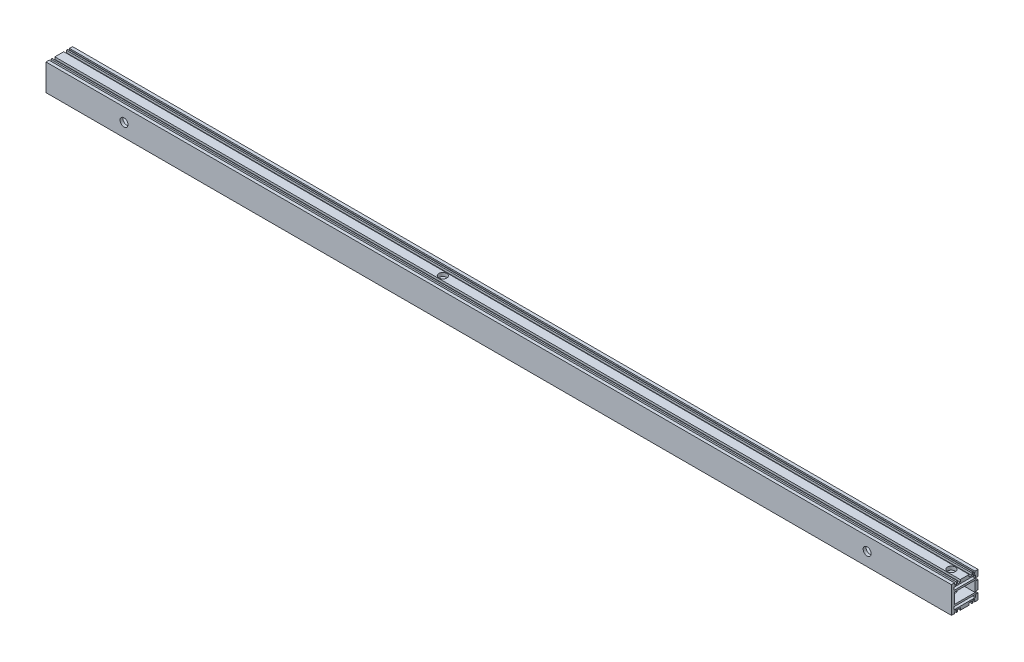
SolidWorks part; units mm, degrees
ref_plane "前视基准面" through (0, 0, 0) normal (0, 0, 1) x (1, 0, 0)
ref_plane "上视基准面" through (0, 0, 0) normal (0, 1, 0) x (1, 0, 0)
ref_plane "右视基准面" through (0, 0, 0) normal (1, 0, 0) x (0, 0, -1)
sketch "草图1" plane through (0, 0, 0) normal (1, 0, 0) x (0, 0, -1)
  line L0 (-15, 15) -> (15, -15) construction
  line L1 (-15, 15) -> (-11.5, 15)
  line L2 (-15, 15) -> (-15, -15)
  line L3 (-15, -15) -> (-11.5, -15)
  line L4 (15, 15) -> (15, 8)
  line L5 (15, 15) -> (-15, -15) construction
  line L6 (-11.5, 15) -> (-11.5, 13.5)
  line L7 (-11.5, 13.5) -> (-11, 13.5)
  line L8 (-11, 13.5) -> (-11, 12)
  line L9 (-11, 12) -> (-9.5, 12)
  line L10 (-9.5, 12) -> (-9.5, 15)
  line L11 (-9.5, 15) -> (-8, 15)
  line L12 (-8, 15) -> (-8, 12.5)
  line L13 (-8, 12.5) -> (-5, 12.5)
  line L14 (-5, 12.5) -> (-5, 15)
  line L15 (-5, 15) -> (5, 15)
  line L16 (0, 21.5201) -> (0, -18.309) construction
  line L17 (0, 55) -> (0, -55) construction
  line L18 (5, 12.5) -> (5, 15)
  line L19 (8, 12.5) -> (5, 12.5)
  line L20 (8, 15) -> (8, 12.5)
  line L21 (9.5, 15) -> (8, 15)
  line L22 (9.5, 12) -> (9.5, 15)
  line L23 (11, 12) -> (9.5, 12)
  line L24 (11, 13.5) -> (11, 12)
  line L25 (11.5, 13.5) -> (11, 13.5)
  line L26 (11.5, 15) -> (11.5, 13.5)
  line L27 (8, 15) -> (9.5, 15)
  line L28 (11.5, 15) -> (15, 15)
  line L29 (-19.8303, 0) -> (22.13, 0) construction
  line L30 (55, 0) -> (-55, 0) construction
  line L31 (8, -15) -> (9.5, -15)
  line L32 (11.5, -15) -> (11.5, -13.5)
  line L33 (11.5, -13.5) -> (11, -13.5)
  line L34 (11, -13.5) -> (11, -12)
  line L35 (11, -12) -> (9.5, -12)
  line L36 (9.5, -12) -> (9.5, -15)
  line L37 (9.5, -15) -> (8, -15)
  line L38 (8, -15) -> (8, -12.5)
  line L39 (8, -12.5) -> (5, -12.5)
  line L40 (5, -12.5) -> (5, -15)
  line L41 (-5, -15) -> (5, -15)
  line L42 (-5, -12.5) -> (-5, -15)
  line L43 (-8, -12.5) -> (-5, -12.5)
  line L44 (-8, -15) -> (-8, -12.5)
  line L45 (-9.5, -15) -> (-8, -15)
  line L46 (-9.5, -12) -> (-9.5, -15)
  line L47 (-11, -12) -> (-9.5, -12)
  line L48 (-11, -13.5) -> (-11, -12)
  line L49 (-11.5, -13.5) -> (-11, -13.5)
  line L50 (-11.5, -15) -> (-11.5, -13.5)
  line L51 (-9.5, -15) -> (-8, -15)
  line L52 (-5, -15) -> (5, -15)
  line L53 (8, -15) -> (9.5, -15)
  line L54 (11.5, -15) -> (15, -15)
  line L55 (15, 8) -> (12.5, 8)
  line L56 (12.5, 8) -> (12.5, 5)
  line L57 (12.5, 5) -> (15, 5)
  line L58 (12.5, -5) -> (15, -5)
  line L59 (12.5, -8) -> (12.5, -5)
  line L60 (15, -8) -> (12.5, -8)
  line L61 (15, 5) -> (15, -5)
  line L62 (15, -8) -> (15, -15)
  line L63 (12, -10.5) -> (12, -8.5)
  line L64 (-11.5, 11) -> (11.5, 11)
  line L65 (-12, 10.5) -> (-12, 8.5)
  line L66 (-11.5, 8) -> (11.5, 8)
  line L67 (12, 10.5) -> (12, 8.5)
  line L68 (-11.5, -8) -> (11.5, -8)
  line L69 (-12, -10.5) -> (-12, -8.5)
  line L70 (-11.5, -11) -> (11.5, -11)
  line L72 (-11.75, 6) -> (11.75, 6)
  line L73 (-11.75, 6) -> (-11.75, -6)
  line L74 (-11.75, -6) -> (11.75, -6)
  line L75 (11.75, 6) -> (11.75, -6)
  arc A0 (12, 8.5) -> (11.5, 8) centre (11.5, 8.5) cw
  arc A1 (11.5, 11) -> (12, 10.5) centre (11.5, 10.5) cw
  arc A2 (-11.5, 11) -> (-12, 10.5) centre (-11.5, 10.5) ccw
  arc A3 (-11.5, 8) -> (-12, 8.5) centre (-11.5, 8.5) cw
  arc A8 (-11.5, -8) -> (-12, -8.5) centre (-11.5, -8.5) ccw
  arc A9 (-11.5, -11) -> (-12, -10.5) centre (-11.5, -10.5) cw
  arc A10 (11.5, -11) -> (12, -10.5) centre (11.5, -10.5) ccw
  arc A11 (12, -8.5) -> (11.5, -8) centre (11.5, -8.5) ccw
  point P69 (12, 11)
  point P72 (-12, 11)
  point P77 (-11, -13.5)
  point P80 (11, -13.5)
  point P83 (11, 13.5)
  point P86 (-11, 13.5)
  point P99 (-12, -11)
  point P100 (12, -11)
  dimension "D17" = 0.5
  dimension "D1" = 3.5
  dimension "D2" = 1.5
  dimension "D3" = 0.5
  dimension "D4" = 1.5
  dimension "D5" = 3
  dimension "D6" = 30
  dimension "D7" = 30
  dimension "D8" = 1.5
  dimension "D9" = 2.5
  dimension "D10" = 3
  dimension "D11" = 2.5
  dimension "D12" = 7
  dimension "D13" = 3
  dimension "D14" = 4
  dimension "D15" = 3
  dimension "D16" = 24
  dimension "D19" = 23.5
  dimension "D20" = 12
extrude "凸台-拉伸1" add sketch "草图1" along normal mid plane 1021 contours L2 L3 L50 L49 L48 L47 L46 L45 L44 L43 L42 L41 L40 L39 L38 L31 L36 L35 L34 L33 L32 L54 L62 L60 L59 L58 L61 L57 L56 L55 L4 L28 L26 L25 L24 L23 L22 L21 L20 L19 L18 L15 L14 L13 region at (0, 14.5757, 13.25)
hole_wizard "M6 螺纹孔1" positions "草图3" profile "草图2" tap size "M6" standard "GB"
sketch "草图3" plane through (0, -15, 0) normal (0, -1, 0) x (-1, 0, 0)
  point P0 (-460.5, 0)
  point P3 (-445.5, 0)
  point P6 (133, 0)
  point P9 (148, 0)
  point P12 (218, 0)
  point P15 (233, 0)
  point P18 (445.5, 0)
  point P21 (460.5, 0)
sketch "草图2" plane through (460.5, -15, 0) normal (1, 0, 0) x (0, 0, -1)
  line L0 (0, 0) -> (0, 20.5022)
  line L1 (0, 20.5022) -> (2.5, 19)
  line L2 (2.5, 19) -> (2.5, 0)
  line L5 (2.5, 0) -> (0, 0)
  line L10 (0, 20.5022) -> (-2.5, 19) construction
  line L11 (0, -6.35) -> (0, 107.95) construction
  dimension "螺纹孔钻头直径" = 5
  dimension "螺纹孔钻头深度" = 19
  dimension "导头角度" = 118
cosmetic thread "孔螺蚊线1" parameters "D1"=9, "D2"=6
cosmetic thread "孔螺蚊线2" parameters "D1"=9, "D2"=6
cosmetic thread "孔螺蚊线3" parameters "D1"=9, "D2"=6
cosmetic thread "孔螺蚊线4" parameters "D1"=9, "D2"=6
cosmetic thread "孔螺蚊线5" parameters "D1"=9, "D2"=6
cosmetic thread "孔螺蚊线6" parameters "D1"=9, "D2"=6
cosmetic thread "孔螺蚊线7" parameters "D1"=9, "D2"=6
cosmetic thread "孔螺蚊线8" parameters "D1"=9, "D2"=6
hole_wizard "M6 螺纹孔2" positions "草图5" profile "草图4" tap size "M6" standard "GB"
sketch "草图5" plane through (0, 0, -15) normal (0, 0, -1) x (-1, 0, 0)
  line L0 (-510.5, -15) -> (510.5, -15) construction
  line L1 (510.5, 5) -> (510.5, -5) construction
  point P0 (460.5, 0)
  point P3 (445.5, 0)
  point P6 (-142.5, 0)
  point P9 (-157.5, 0)
  point P12 (-445.5, 0)
  point P15 (-460.5, 0)
  point P18 (380.5, 0)
  dimension "D1" = 15
  dimension "D2" = 130
sketch "草图4" plane through (-460.5, 0, -15) normal (1, 0, 0) x (0, 1, 0)
  line L0 (0, 0) -> (0, 20.5022)
  line L1 (0, 20.5022) -> (2.5, 19)
  line L2 (2.5, 19) -> (2.5, 0)
  line L5 (2.5, 0) -> (0, 0)
  line L10 (0, 20.5022) -> (-2.5, 19) construction
  line L11 (0, -6.35) -> (0, 107.95) construction
  dimension "螺纹孔钻头直径" = 5
  dimension "螺纹孔钻头深度" = 19
  dimension "导头角度" = 118
cosmetic thread "孔螺蚊线9" parameters "D1"=3.25, "D2"=6
cosmetic thread "孔螺蚊线10" parameters "D1"=3.25, "D2"=6
cosmetic thread "孔螺蚊线11" parameters "D1"=3.25, "D2"=6
cosmetic thread "孔螺蚊线12" parameters "D1"=3.25, "D2"=6
cosmetic thread "孔螺蚊线13" parameters "D1"=3.25, "D2"=6
cosmetic thread "孔螺蚊线14" parameters "D1"=3.25, "D2"=6
cosmetic thread "孔螺蚊线17" parameters "D1"=3.25, "D2"=6
hole_wizard "M6 螺纹孔3" positions "草图7" profile "草图6" tap size "M6" standard "GB"
sketch "草图7" plane through (0, -15, 0) normal (0, -1, 0) x (-1, 0, 0)
  line L0 (-510.5, 15) -> (510.5, 15) construction
  line L2 (-510.5, -5) -> (-510.5, 5) construction
  line L3 (-510.5, -15) -> (510.5, -15) construction
  line L4 (-510.5, -5) -> (-510.5, 5) construction
  point P0 (-262.5, 0)
  point P2 (-211.5, 0)
  point P13 (-160.5, 0)
  dimension "D1" = 15
  dimension "D2" = 15
  dimension "D3" = 51
  dimension "D4" = 248
  dimension "D5" = 15
  dimension "D6" = 350
sketch "草图6" plane through (262.5, -15, 0) normal (1, 0, 0) x (0, 0, -1)
  line L0 (0, 0) -> (0, 18.5022)
  line L1 (0, 18.5022) -> (2.5, 17)
  line L2 (2.5, 17) -> (2.5, 0)
  line L5 (2.5, 0) -> (0, 0)
  line L10 (0, 18.5022) -> (-2.5, 17) construction
  line L11 (0, -6.35) -> (0, 107.95) construction
  dimension "螺纹孔钻头直径" = 5
  dimension "螺纹孔钻头深度" = 17
  dimension "导头角度" = 118
cosmetic thread "孔螺蚊线15" parameters "D1"=9, "D2"=6
cosmetic thread "孔螺蚊线16" parameters "D1"=9, "D2"=6
cosmetic thread "孔螺蚊线21" parameters "D1"=9, "D2"=6
sketch "草图9" plane through (0, 0, 15) normal (0, 0, 1) x (1, 0, 0)
  line L0 (-510.5, 15) -> (-510.5, -15) construction
  line L1 (510.5, 15) -> (-510.5, 15) construction
  line L2 (510.5, 15) -> (510.5, -15) construction
  circle A0 centre (415.5, 0) radius 4.5
  circle A1 centre (-422.5, 0) radius 4.5
  dimension "D2" = 9
  dimension "D6" = 9
  dimension "D1" = 88
  dimension "D3" = 15
  dimension "D4" = 15
  dimension "D5" = 95
extrude "切除-拉伸1" cut sketch "草图9" against normal through all
sketch "草图10" plane through (0, 15, 0) normal (0, 1, 0) x (1, 0, 0)
  line L0 (510.5, -15) -> (-510.5, -15) construction
  line L1 (510.5, -5) -> (510.5, 5) construction
  line L2 (-510.5, -5) -> (-510.5, 5) construction
  circle A0 centre (495.5, 0) radius 4.5
  circle A1 centre (-78, 0) radius 4.5
  dimension "D3" = 9
  dimension "D6" = 9
  dimension "D1" = 15
  dimension "D2" = 15
  dimension "D4" = 15
  dimension "D5" = 432.5
extrude "切除-拉伸2" cut sketch "草图10" against normal through all
hole_wizard "M4 螺纹孔1" positions "草图12" profile "草图11" tap size "M4" standard "GB"
sketch "草图12" plane through (0, 0, -15) normal (0, 0, -1) x (-1, 0, 0)
  line L0 (-510.5, -15) -> (510.5, -15) construction
  line L1 (-510.5, 5) -> (-510.5, -5) construction
  point P0 (-429.5, 0)
  point P2 (-401.5, 0)
  dimension "D1" = 15
  dimension "D2" = 15
  dimension "D3" = 81
  dimension "D4" = 109
sketch "草图11" plane through (429.5, 0, -15) normal (1, 0, 0) x (0, 1, 0)
  line L0 (0, 0) -> (0, 12.4914)
  line L1 (0, 12.4914) -> (1.65, 11.5)
  line L2 (1.65, 11.5) -> (1.65, 0)
  line L5 (1.65, 0) -> (0, 0)
  line L10 (0, 12.4914) -> (-1.65, 11.5) construction
  line L11 (0, -6.35) -> (0, 107.95) construction
  dimension "螺纹孔钻头直径" = 3.3
  dimension "螺纹孔钻头深度" = 11.5
  dimension "导头角度" = 118
cosmetic thread "孔螺蚊线18" parameters "D1"=3.25, "D2"=4
cosmetic thread "孔螺蚊线19" parameters "D1"=3.25, "D2"=4
hole_wizard "M4 螺纹孔2" positions "草图14" profile "草图13" tap size "M4" standard "GB"
sketch "草图14" plane through (0, 0, -15) normal (0, 0, -1) x (-1, 0, 0)
  line L0 (-510.5, -15) -> (510.5, -15) construction
  line L1 (-510.5, 5) -> (-510.5, -5) construction
  point P0 (-343.5, 0)
  dimension "D1" = 15
  dimension "D2" = 167
sketch "草图13" plane through (343.5, 0, -15) normal (1, 0, 0) x (0, 1, 0)
  line L0 (0, 0) -> (0, 12.4914)
  line L1 (0, 12.4914) -> (1.65, 11.5)
  line L2 (1.65, 11.5) -> (1.65, 0)
  line L5 (1.65, 0) -> (0, 0)
  line L10 (0, 12.4914) -> (-1.65, 11.5) construction
  line L11 (0, -6.35) -> (0, 107.95) construction
  dimension "螺纹孔钻头直径" = 3.3
  dimension "螺纹孔钻头深度" = 11.5
  dimension "导头角度" = 118
cosmetic thread "孔螺蚊线20" parameters "D1"=3.25, "D2"=4
